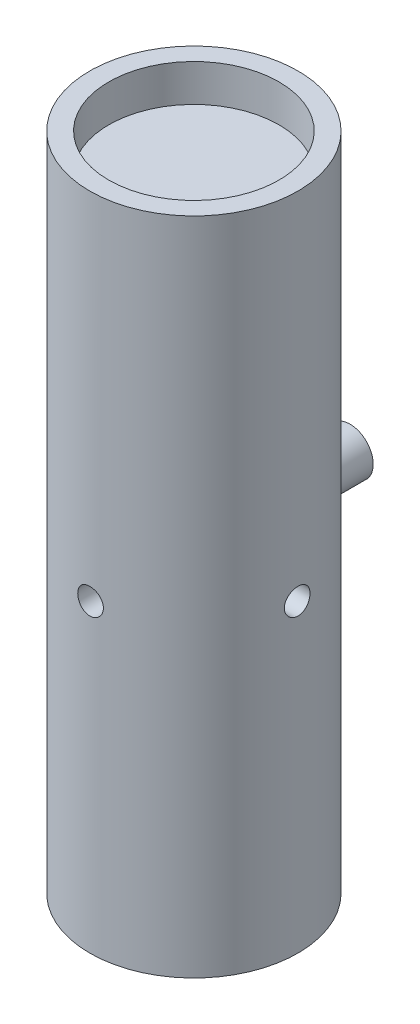
SolidWorks part; units mm, degrees
ref_plane "Front" through (0, 0, 0) normal (0, 0, 1) x (1, 0, 0)
ref_plane "Top" through (0, 0, 0) normal (0, 1, 0) x (1, 0, 0)
ref_plane "Right" through (0, 0, 0) normal (1, 0, 0) x (0, 0, -1)
sketch "Sketch1" plane through (0, 0, 0) normal (0, 1, 0) x (1, 0, 0)
  circle A0 centre (0, 0) radius 14
  dimension "D1" = 28
extrude "Extrude1" add sketch "Sketch1" along normal blind 88.76
hole_wizard "M4x0.7 Tapped Hole1" positions "Sketch3" profile "Sketch2" tap size "M4x0.7" standard "Ansi Metric"
sketch "Sketch3" plane through (-1.1206, 0, -3.9038) normal (0, 1, 0) x (-1, 0, 0)
  circle A0 centre (-1.1206, 3.9038) radius 14 construction
  point P0 (-1.1206, 3.9038)
sketch "Sketch2" plane through (0, 0, 0) normal (1, 0, 0) x (0, 0, -1)
  line L0 (0, 0) -> (0, 6.0204)
  line L1 (0, 6.0204) -> (1.65, 5.029)
  line L2 (1.65, 5.029) -> (1.65, 0)
  line L5 (1.65, 0) -> (0, 0)
  line L10 (0, 6.0204) -> (-1.65, 5.029) construction
  line L11 (0, -6.35) -> (0, 107.95) construction
  dimension "Tap Drill Dia." = 3.3
  dimension "Tap Drill Depth" = 5.029
  dimension "Drill Angle" = 118
cosmetic thread "Hole Thread1" parameters "D1"=2.921, "D2"=4
ref_plane "Plane1" through (-14, 0, 0) normal (1, 0, 0) x (0, 0, -1)
ref_plane "Plane2" through (0, 41, 0) normal (0, -1, 0) x (1, 0, 0)
hole_wizard "#8-32 Tapped Hole1" positions "Sketch5" profile "Sketch4" tap size "#8-32" standard "Ansi Inch"
sketch "Sketch5" plane through (-14, 0, 0) normal (1, 0, 0) x (0, 0, -1)
  line L0 (-15.4, 41) -> (15.4, 41) construction
  line L2 (0, 50) -> (0, -50) construction
  point P0 (0, 41)
sketch "Sketch4" plane through (-14, 41, 0) normal (0, 1, 0) x (0, 0, 1)
  line L0 (0, 0) -> (0, 11.7458)
  line L1 (0, 11.7458) -> (1.7272, 10.708)
  line L2 (1.7272, 10.708) -> (1.7272, 0)
  line L5 (1.7272, 0) -> (0, 0)
  line L10 (0, 11.7458) -> (-1.7272, 10.708) construction
  line L11 (0, -6.35) -> (0, 107.95) construction
  dimension "Tap Drill Dia." = 3.4544
  dimension "Tap Drill Depth" = 10.708
  dimension "Drill Angle" = 118
cosmetic thread "Hole Thread2" parameters "D1"=8.331, "D2"=4.1656
pattern_circular "CirPattern1" count 3 every 90 about axis through (0, 0, 0) along (0, 1, 0) of "#8-32 Tapped Hole1"
sketch "Sketch6" plane through (0, 88.76, 0) normal (0, 1, 0) x (1, 0, 0)
  circle A0 centre (0, 0) radius 11.4472
extrude "Extrude2" cut sketch "Sketch6" against normal blind 5
ref_plane "Plane3" through (0, 0, -14) normal (0, 0, 1) x (1, 0, 0)
sketch "Sketch7" plane through (0, 0, -14) normal (0, 0, 1) x (1, 0, 0)
  line L0 (-15.4, 41) -> (15.4, 41) construction
  circle A0 centre (0, 41) radius 3.1186
extrude "Extrude3" add sketch "Sketch7" along normal blind 1 and the other way blind 7
ref_axis "Axis1" through (0, 320.3736, 0) along (0, -1, 0)
ref_point "Point1"
ref_plane "Plane4" through (14, 0, 0) normal (1, 0, 0) x (0, 0, -1)
